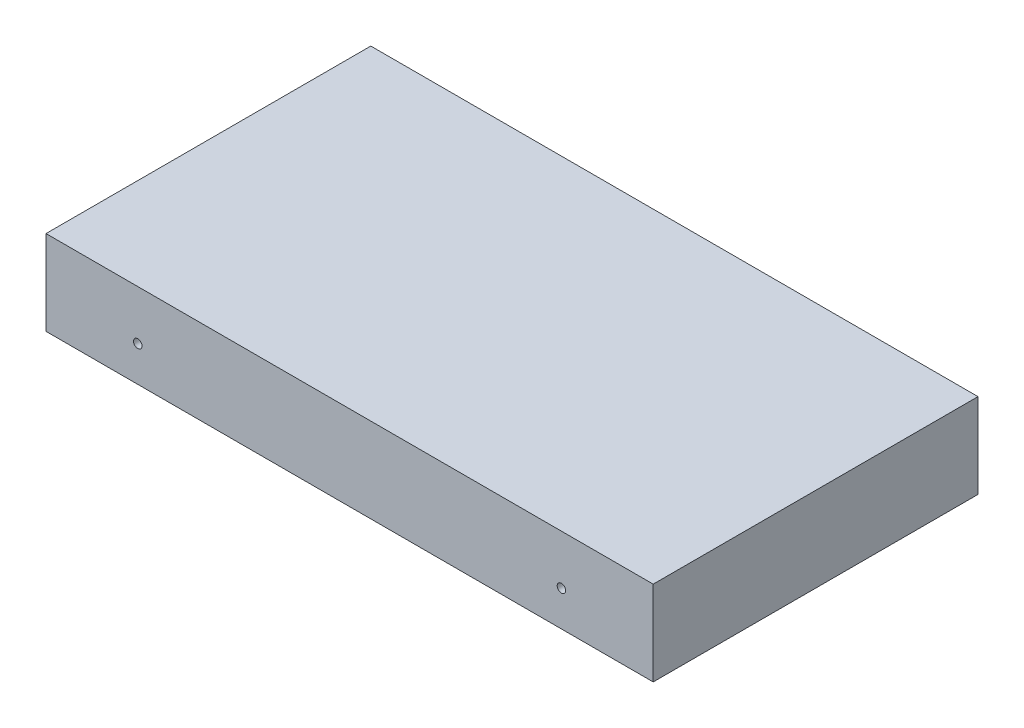
SolidWorks part; units mm, degrees
ref_plane "Front" through (0, 0, 0) normal (0, 0, 1) x (1, 0, 0)
ref_plane "Top" through (0, 0, 0) normal (0, 1, 0) x (1, 0, 0)
ref_plane "Right" through (0, 0, 0) normal (1, 0, 0) x (0, 0, -1)
sketch "Sketch1" plane through (0, 0, 0) normal (0, 1, 0) x (1, 0, 0)
  line L1 (-107.5, 57.5) -> (107.5, 57.5)
  line L2 (-107.5, 57.5) -> (-107.5, -57.5)
  line L3 (-107.5, -57.5) -> (107.5, -57.5)
  line L4 (107.5, 57.5) -> (107.5, -57.5)
  point P4 (0, 57.5)
  point P6 (-107.5, 0)
  dimension "D1" = 215
  dimension "D2" = 115
extrude "Boss-Extrude1" add sketch "Sketch1" along normal blind 30
hole_wizard "Ø3.0 (3) Diameter Hole1" positions "Sketch2" profile "Sketch3" hole size "Ø3.0" standard "ANSI Metric"
sketch "Sketch2" plane through (0, 0, 57.5) normal (0, 0, 1) x (1, 0, 0)
  line L0 (-75, 12.5) -> (75, 12.5) construction
  line L3 (-107.5, 30) -> (107.5, 30) construction
  point P0 (-75, 12.5)
  point P2 (75, 12.5)
  point P10 (0, 12.5)
  dimension "D1" = 150
  dimension "D2" = 17.5
sketch "Sketch3" plane through (-75, 12.5, 57.5) normal (1, 0, 0) x (0, -1, 0)
  line L0 (0, 0) -> (0, 8.0133)
  line L1 (0, 8.0133) -> (1.5, 7.112)
  line L2 (1.5, 7.112) -> (1.5, 0)
  line L5 (1.5, 0) -> (0, 0)
  line L10 (0, 8.0133) -> (-1.5, 7.112) construction
  line L11 (0, -6.35) -> (0, 107.95) construction
  dimension "Hole Dia." = 3
  dimension "Hole Depth" = 7.112
  dimension "Drill Angle" = 118
mirror "Mirror1" about plane through (0, 0, 0) normal (0, 0, 1) of "Ø3.0 (3) Diameter Hole1"
